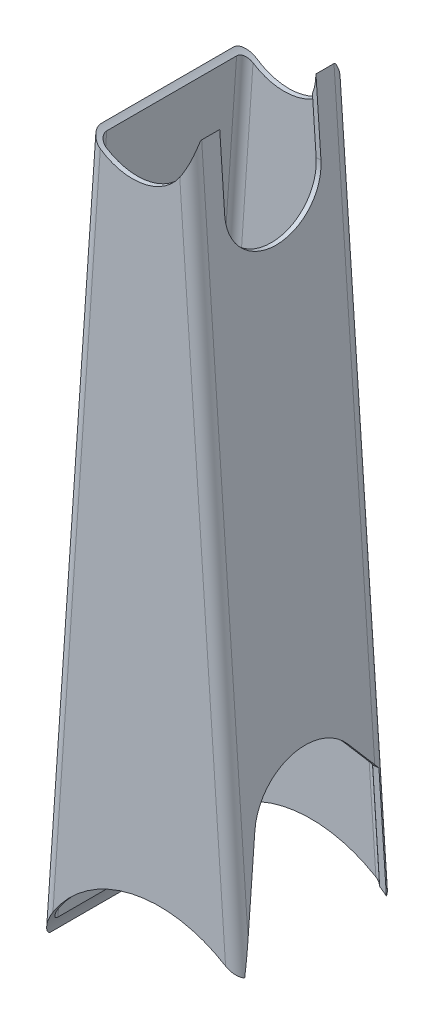
SolidWorks part; units mm, degrees
ref_plane "前视基准面" through (0, 0, 0) normal (0, 0, 1) x (1, 0, 0)
ref_plane "上视基准面" through (0, 0, 0) normal (0, 1, 0) x (1, 0, 0)
ref_plane "右视基准面" through (0, 0, 0) normal (1, 0, 0) x (0, 0, -1)
other "Configuration Table"
sketch "草图1" plane through (0, 0, 0) normal (0, 0, 1) x (1, 0, 0)
  line L0 (-58.513, 634.2522) -> (-100.21, 31.3522)
  line L1 (25.187, 664.2936) -> (65.59, 81.9936)
  line L2 (-22.3077, 665) -> (0, 0) construction
  line L3 (0, 0) -> (0, 324.7291) construction
  arc A0 (65.59, 81.9936) -> (-100.21, 31.3522) centre (0, 0) ccw
  arc A1 (-58.513, 634.2522) -> (25.187, 664.2936) centre (-22.3077, 665) ccw
  point P1 (86.8322, 59.0354)
  dimension "D1" = 105
  dimension "D2" = 95
  dimension "D3" = 83.7
  dimension "D4" = 165.8
  dimension "D5" = 602.9
  dimension "D6" = 665
  dimension "D7" = 583.7
  dimension "D8" = 582.3
extrude "凸台-拉伸1" add sketch "草图1" along normal mid plane 130
shell "抽壳1" thickness 4 removed face at (-23.991, 78.5466, 0) removed face at (-11.4622, 634.7827, 0)
sketch "草图2" plane through (70.9376, 4.922, 0) normal (0.9976, 0.0692, 0) x (0, 0, -1)
  line L0 (-40, 660.9569) -> (-40, 600.9569)
  line L1 (-65, 660.9569) -> (65, 660.9569) construction
  line L2 (40, 600.9569) -> (40, 660.9569)
  line L3 (-40, 660.9569) -> (40, 660.9569)
  arc A0 (-40, 600.9569) -> (40, 600.9569) centre (0, 600.9569) ccw
  point P6 (0, 660.9569)
  point P8 (0, 0)
  point P9 (0, 660.9569)
  dimension "D2" = 40
  dimension "D1" = 60
extrude "切除-拉伸1" cut sketch "草图2" against normal up to next
sketch "草图3" plane through (70.9376, 4.922, 0) normal (0.9976, 0.0692, 0) x (0, 0, -1)
  line L1 (-65, 77.2569) -> (65, 77.2569) construction
  line L5 (0, 77.2569) -> (0, 560.9569) construction
  line L11 (-58.9504, 77.2569) -> (-44.5057, 173.9083)
  line L12 (34.3201, 196.3624) -> (59.0034, 167.2569)
  line L13 (59.0034, 167.2569) -> (59.0034, 77.2569)
  line L14 (59.0034, 77.2569) -> (-58.9504, 77.2569)
  arc A1 (-40, 600.9569) -> (40, 600.9569) centre (0, 600.9569) ccw construction
  arc A2 (-44.5057, 173.9083) -> (34.3201, 196.3624) centre (0, 167.2569) cw
  point P11 (0, 0)
  point P14 (0, 129.4616)
  dimension "D2" = 8.5
  dimension "D1" = 45
  dimension "D3" = 90
  dimension "D4" = 40.3
extrude "切除-拉伸2" cut sketch "草图3" against normal up to next
fillet "圆角2" radius 10 4 edges at (45.3885, 373.1436, -65) (45.3885, 373.1436, 65) (-79.3615, 332.8022, 65) (-79.3615, 332.8022, -65)
fillet "圆角3" radius 7 4 edges at (-75.0493, 337.1775, 61) (41.8123, 366.8979, -61) (-75.0493, 337.1775, -61) (41.8123, 366.8979, 61)
